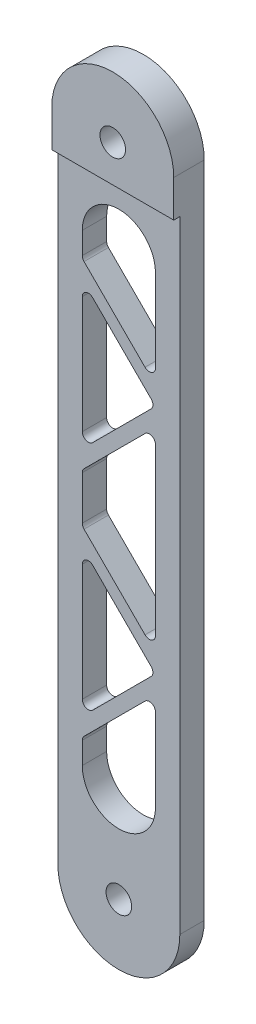
SolidWorks part; units mm, degrees
material "PLA"
ref_plane "Alzado" through (0, 0, 0) normal (0, 0, 1) x (1, 0, 0)
ref_plane "Planta" through (0, 0, 0) normal (0, 1, 0) x (1, 0, 0)
ref_plane "Vista lateral" through (0, 0, 0) normal (1, 0, 0) x (0, 0, -1)
sketch "Croquis1" plane through (0, 0, 0) normal (0, 0, 1) x (1, 0, 0)
  line L0 (0, 54) -> (0, -54) construction
  line L1 (10, 54) -> (10, -54)
  line L2 (-10, 54) -> (-10, -54)
  line L3 (0, 38) -> (0, -38) construction
  line L4 (6, 38) -> (6, -38)
  line L5 (-6, 38) -> (-6, -38)
  line L6 (-10, -47.95) -> (10, -47.95)
  line L7 (0, 51.9) -> (0, 44) construction
  line L8 (-10, 47.95) -> (10, 47.95)
  line L9 (0, -51.9) -> (0, -44) construction
  line L10 (0, 0) -> (0, -38) construction
  line L11 (-6, 0) -> (6, 0) construction
  line L12 (-6, -34) -> (6, -22)
  line L13 (-6, -31) -> (6, -19)
  line L14 (-6, -19) -> (6, -19) construction
  line L16 (-6, -7) -> (6, -19)
  line L17 (-6, -4) -> (6, -16)
  line L18 (-6, 4) -> (6, 16)
  line L19 (-6, 7) -> (6, 19)
  line L20 (-6, 31) -> (6, 19)
  line L21 (-6, 34) -> (6, 22)
  arc A0 (10, 54) -> (-10, 54) centre (0, 54) ccw
  arc A1 (-10, -54) -> (10, -54) centre (0, -54) ccw
  circle A2 centre (0, 54) radius 2.1
  circle A3 centre (0, -54) radius 2.1
  arc A4 (6, 38) -> (-6, 38) centre (0, 38) ccw
  arc A5 (-6, -38) -> (6, -38) centre (0, -38) ccw
  point P2 (0, 0)
  point P14 (0, 0)
  point P23 (0, 47.95)
  point P28 (0, -47.95)
  point P37 (0, -19)
  dimension "D1" = 4.2
  dimension "D2" = 20
  dimension "D3" = 108
  dimension "D4" = 4
  dimension "D5" = 16
  dimension "D6" = 135
  dimension "D7" = 3
extrude "Saliente-Extruir1" add sketch "Croquis1" along normal blind 4 contours L2 A1 L1 L8 A5 L5 A4 L4 A3 | L13 L5 L12 L4 | L17 L5 L16 L4 | L19 L5 L18 L4 | L21 L5 L20 L4 | L2 A1 L1 A0 | A3 | L5 A5 L4 A4 | A2 region at (9.0204, 0, 0) region at (0, 26.5, 0) region at (0, 11.5, 0) region at (0, -11.5, 0) region at (0, -26.5, 0)
extrude "Saliente-Extruir3" add sketch "Croquis1<6>" along normal blind 5 contours L1 A0 L2 L8 A2 region at (9.7436, 50.975, 0)
sketch "Croquis1<6>" plane through (0, 0, 0) normal (0, 0, 1) x (1, 0, 0) same geometry as "Croquis1"
fillet "Redondeo1" radius 1 14 edges at (6, 22, 2) (6, 16, 2) (6, 19, 2) (-6, 31, 2) (-6, 7, 2) (6, -22, 2) (6, -16, 2) (6, -19, 2) (-6, -31, 2) (-6, -7, 2) (-6, 34, 2) (-6, -4, 2) (-6, -34, 2) (-6, 4, 2)
